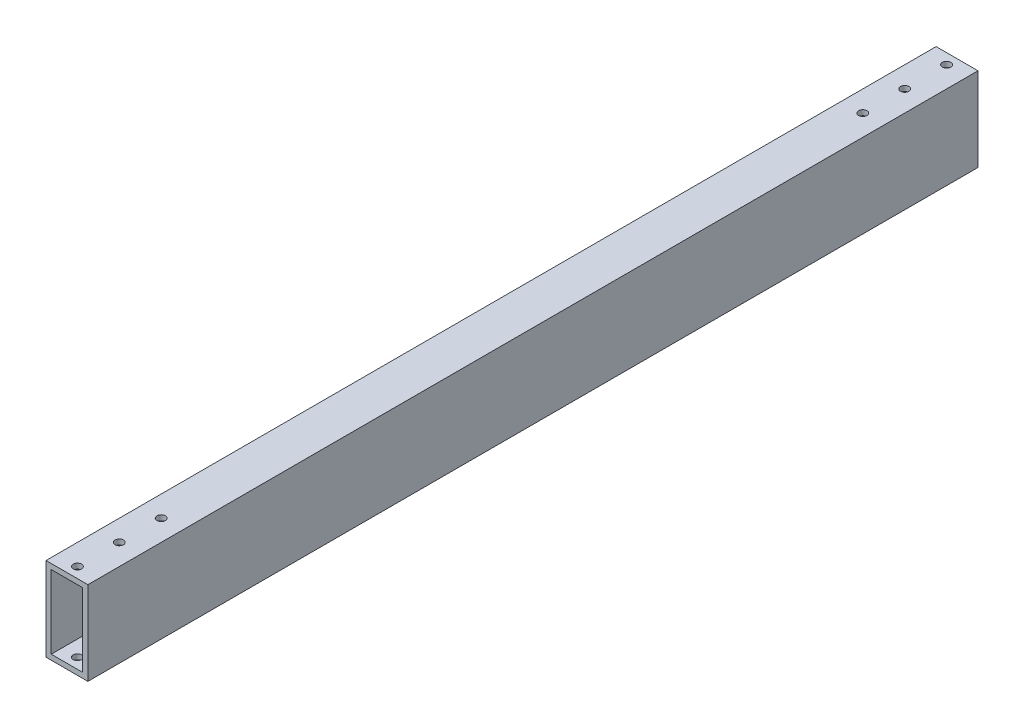
SolidWorks part; units mm, degrees
material "6061-T6 (SS)"
ref_plane "Front" through (0, 0, 0) normal (0, 0, 1) x (1, 0, 0)
ref_plane "Top" through (0, 0, 0) normal (0, 1, 0) x (1, 0, 0)
ref_plane "Right" through (0, 0, 0) normal (1, 0, 0) x (0, 0, -1)
sketch "Sketch1" plane through (0, 0, 0) normal (0, 0, 1) x (1, 0, 0)
  line L1 (-12.7, -25.4) -> (12.7, -25.4)
  line L2 (-12.7, -25.4) -> (-12.7, 25.4)
  line L3 (-12.7, 25.4) -> (12.7, 25.4)
  line L4 (12.7, -25.4) -> (12.7, 25.4)
  line L5 (-12.7, -25.4) -> (12.7, 25.4) construction
  line L6 (-12.7, 25.4) -> (12.7, -25.4) construction
  point P0 (0, 0)
  dimension "D1" = 25.4
  dimension "D2" = 50.8
extrude "Extrude-Thin1" add sketch "Sketch1" along normal blind 539.75 thin thin type one direction reverse wall 3.175
hole_wizard "#10 Clearance Hole1" positions "Sketch2" profile "Sketch3" hole size "#10" standard "ANSI Inch" end condition through all
sketch "Sketch2" plane through (0, 25.4, 0) normal (0, 1, 0) x (1, 0, 0)
  line L0 (12.7, -539.75) -> (-12.7, -539.75) construction
  line L1 (-12.7, -539.75) -> (-12.7, 0) construction
  point P0 (0, -533.4)
  point P2 (0, -508)
  point P4 (0, -482.6)
  point P13 (0, -6.35)
  point P15 (0, -31.75)
  point P17 (0, -57.15)
  dimension "D1" = 6.35
  dimension "D2" = 25.4
  dimension "D3" = 25.4
  dimension "D4" = 12.7
  dimension "D5" = 6.35
  dimension "D6" = 25.4
  dimension "D7" = 25.4
sketch "Sketch3" plane through (0, 25.4, 533.4) normal (1, 0, 0) x (0, 0, 1)
  line L0 (0, 0) -> (0, 50.8)
  line L1 (0, 50.8) -> (2.5527, 50.8)
  line L2 (2.5527, 50.8) -> (2.5527, 0)
  line L5 (2.5527, 0) -> (0, 0)
  line L11 (0, -6.35) -> (0, 107.95) construction
  dimension "Thru Hole Dia." = 5.1054
  dimension "Thru Hole Depth" = 50.8
